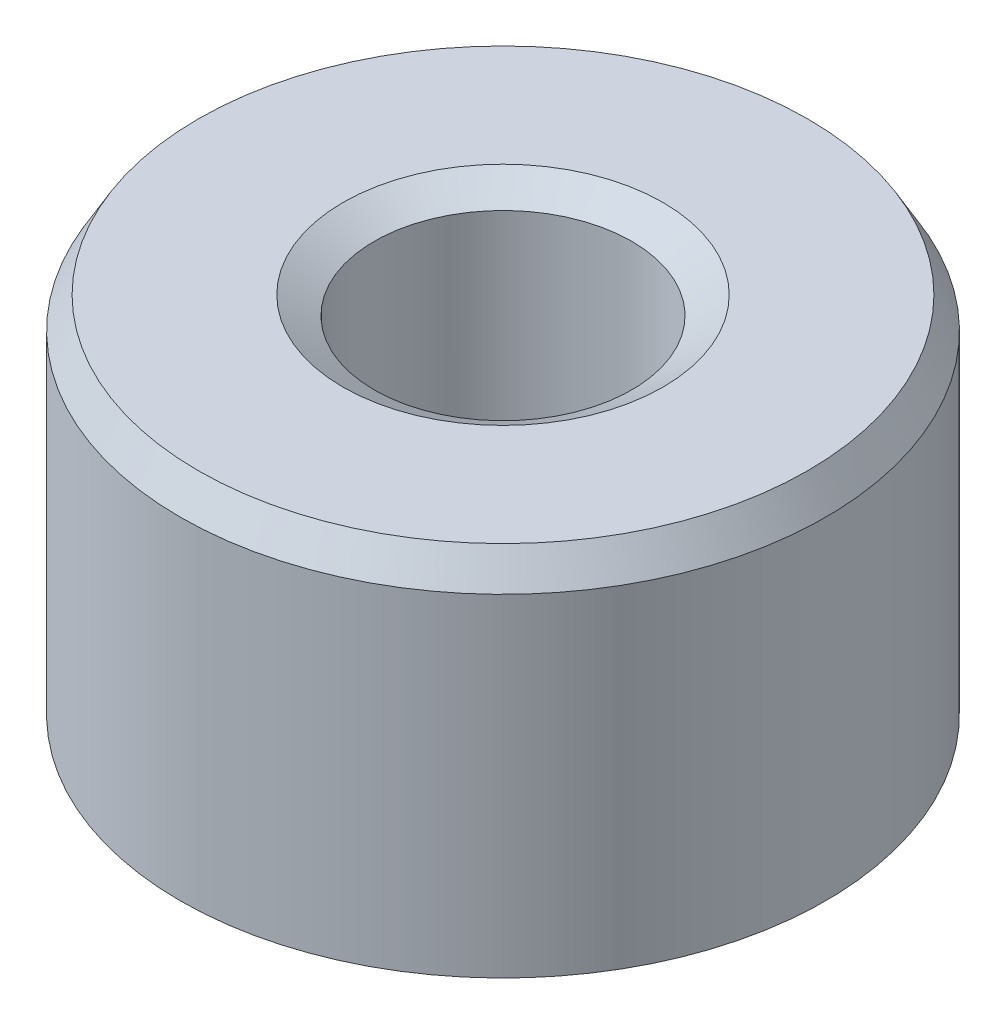
SolidWorks part; units mm, degrees
ref_plane "Front Plane" through (0, 0, 0) normal (0, 0, 1) x (1, 0, 0)
ref_plane "Top Plane" through (0, 0, 0) normal (0, 1, 0) x (1, 0, 0)
ref_plane "Right Plane" through (0, 0, 0) normal (1, 0, 0) x (0, 0, -1)
sketch "Sketch1" plane through (0, 0, 0) normal (0, 1, 0) x (1, 0, 0)
  circle A0 centre (0, 0) radius 35
  dimension "SLEEVE_OD" = 70
extrude "Boss-Extrude1" add sketch "Sketch1" along normal blind 41.3738
sketch "Sketch2" plane through (0, 0, 0) normal (0, 1, 0) x (1, 0, 0)
  circle A0 centre (0, 0) radius 13.9641
  dimension "BORE_D" = 27.9283
extrude "Cut-Extrude1" cut sketch "Sketch2" along normal through all
chamfer "Chamfer1" distance 3.3852 angle 30 4 edges at (0, 41.3738, 13.9641) (0, 0, 13.9641) (0, 0, 35) (0, 41.3738, 35) first distance on face at (0, 41.3738, 13.9641) first distance on face at (0, 0, 13.9641) first distance on face at (0, 41.3738, 35)
